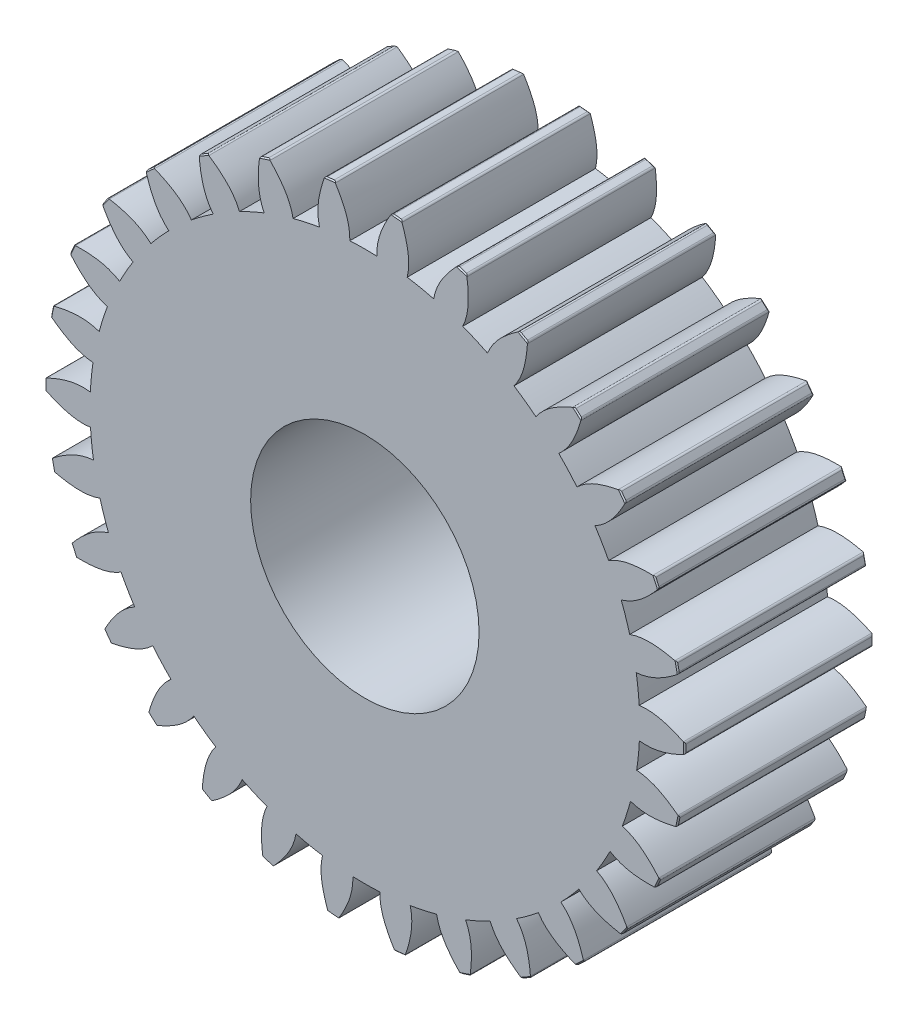
SolidWorks part; units mm, degrees
ref_plane "Front Plane" through (0, 0, 0) normal (0, 0, 1) x (1, 0, 0)
ref_plane "Top Plane" through (0, 0, 0) normal (0, 1, 0) x (1, 0, 0)
ref_plane "Right Plane" through (0, 0, 0) normal (1, 0, 0) x (0, 0, -1)
sketch "Sketch1" plane through (0, 0, 0) normal (0, 0, 1) x (1, 0, 0)
  line L0 (-8.2047, 49.1955) -> (-5.4614, 49.3462) construction
  line L1 (2.7687, 49.7981) -> (13.6078, 47.9827) construction
  line L2 (13.6078, 47.9827) -> (23.7861, 43.8376) construction
  line L3 (23.7861, 43.8376) -> (32.8095, 37.564) construction
  line L4 (2.7687, 49.7981) -> (-8.2043, 50.4082) construction
  line L5 (13.6078, 47.9827) -> (-7.5383, 53.9797) construction
  line L6 (23.7861, 43.8376) -> (-5.1929, 59.5615) construction
  line L7 (32.8095, 37.564) -> (-0.2996, 66.4824) construction
  line L8 (0, 0) -> (-2.6387, 48.0526) construction
  line L10 (0, 0) -> (-5.4614, 49.3462) construction
  arc A0 (13.6299, 54.316) -> (1.4033, 55.9824) centre (0, 0) ccw
  circle A1 centre (0, 0) radius 52.5 construction
  circle A2 centre (0, 0) radius 49.875
  circle A3 centre (0, 0) radius 48.125
  arc A4 (-5.2994, 55.7487) -> (-7.0195, 55.5583) centre (0, 0) ccw
  spline S0 degree 3 poles (-7.9411, 47.4653) (-8.0871, 48.0419) (-8.2303, 49.0251) (-8.2225, 51.2167) (-7.7626, 53.3587) (-7.2091, 55.0384) (-7.0195, 55.5583) knots -0.089037 -0.089037 -0.089037 -0.089037 0 0.062585 0.250087 0.335631 0.335631 0.335631 0.335631
  spline S1 degree 3 poles (-2.6304, 48.0531) (-2.614, 48.6476) (-2.6892, 49.6384) (-3.176, 51.7752) (-4.0933, 53.7648) (-5.0006, 55.2828) (-5.2994, 55.7487) knots -0.089037 -0.089037 -0.089037 -0.089037 0 0.062585 0.250087 0.335631 0.335631 0.335631 0.335631
  dimension "D1" = 112
  dimension "D2" = 99.75
  dimension "55" = 105
  dimension "D3" = 96.25
  dimension "D4" = 10.99
  dimension "D5" = 10.99
  dimension "D6" = 21.98
  dimension "D7" = 32.97
  dimension "D8" = 43.96
extrude "Boss-Extrude1" add sketch "Sketch1" along normal blind 32.97 contours A3 | A2 S1 A4 S0 | A3 S1 A2 S0
chamfer "Chamfer1" distance 0.2 angle 45 2 edges at (-6.1602, 55.6602, 32.97) (-6.1602, 55.6602, 0)
fillet "Fillet1" radius 0.4 2 edges at (-5.2994, 55.7487, 16.485) (-7.0195, 55.5583, 16.485)
pattern_circular "CirPattern1" count 30 over 360 about axis through (0, 0, 32.97) along (0, 0, 1) of "Boss-Extrude1", "Chamfer1", "Fillet1"
sketch "Sketch2" plane through (0, 0, 32.97) normal (0, 0, 1) x (1, 0, 0)
  circle A0 centre (0, 0) radius 20
  dimension "D1" = 40
extrude "Cut-Extrude1" cut sketch "Sketch2" against normal through all
